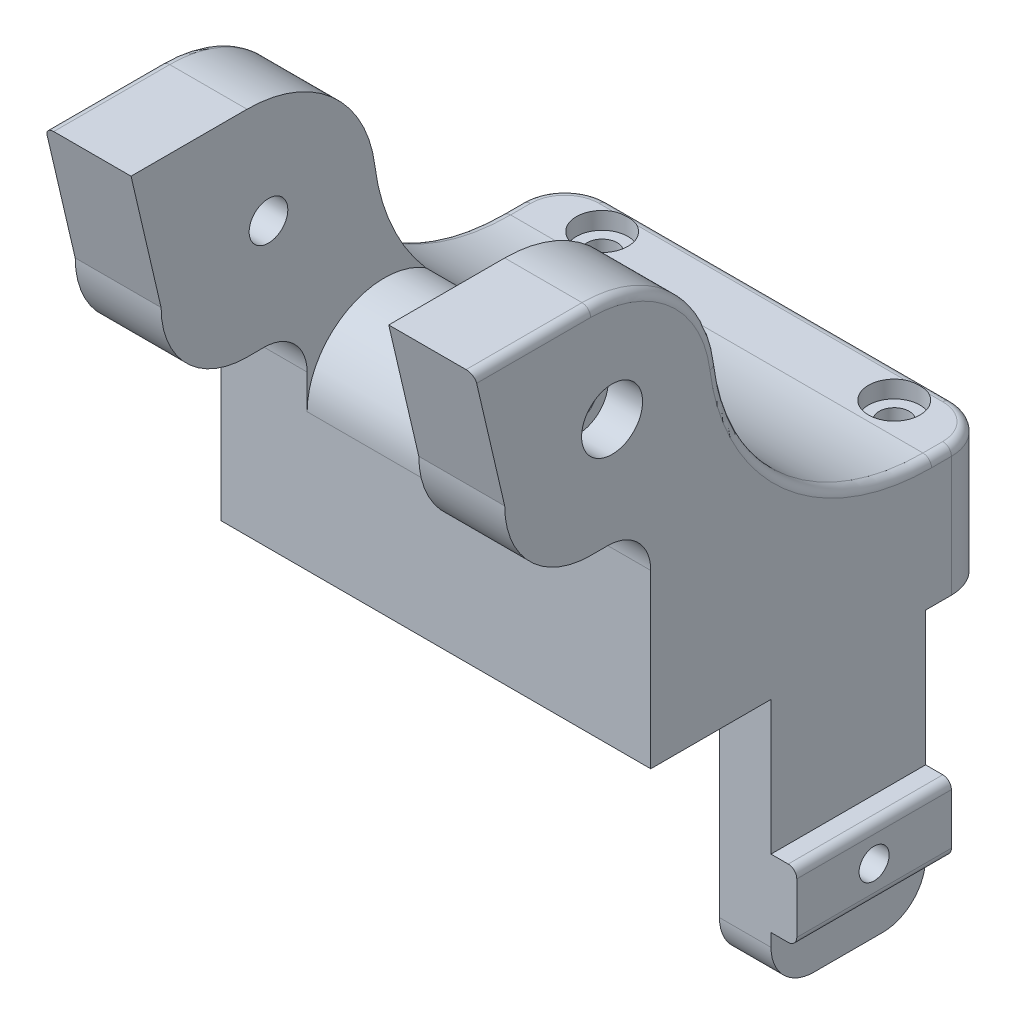
SolidWorks part; units mm, degrees
ref_plane "Alzado" through (0, 0, 0) normal (0, 0, 1) x (1, 0, 0)
ref_plane "Planta" through (0, 0, 0) normal (0, 1, 0) x (1, 0, 0)
ref_plane "Vista lateral" through (0, 0, 0) normal (1, 0, 0) x (0, 0, -1)
sketch "Croquis1" plane through (0, 0, 0) normal (0, 1, 0) x (1, 0, 0)
  line L1 (0, 0) -> (50, 0)
  line L2 (0, 0) -> (0, 40)
  line L3 (0, 40) -> (50, 40)
  line L4 (50, 0) -> (50, 40)
  dimension "D1" = 50
  dimension "D2" = 40
extrude "Saliente-Extruir1" add sketch "Croquis1" along normal blind 25
sketch "Croquis4" plane through (0, 25, 0) normal (0, 1, 0) x (1, 0, 0)
  line L0 (0, 40) -> (0, 0) construction
  line L1 (0, 8) -> (10, 8)
  line L2 (0, 8) -> (0, -17)
  line L3 (0, -17) -> (10, -17)
  line L4 (10, 8) -> (10, -17)
  line L5 (50, 0) -> (50, 40) construction
  line L6 (50, 8) -> (40, 8)
  line L7 (50, 8) -> (50, -17)
  line L8 (50, -17) -> (40, -17)
  line L9 (40, 8) -> (40, -17)
  line L10 (50, 40) -> (0, 40) construction
  dimension "D1" = 10
  dimension "D2" = 10
  dimension "D3" = 25
  dimension "D4" = 25
  dimension "D5" = 32
  dimension "D6" = 32
extrude "Saliente-Extruir3" add sketch "Croquis4" along normal blind 25
sketch "Croquis5" plane through (50, 0, 0) normal (1, 0, 0) x (0, 0, -1)
  line L0 (8, 50) -> (-17, 25) construction
  circle A0 centre (-4.5, 37.5) radius 2.25
  dimension "D1" = 4.5
extrude "Cortar-Extruir2" cut sketch "Croquis5" against normal up to surface (50 mm away) up to face at (0, 25, -7.75)
fillet "Redondeo4" radius 15 2 edges at (5, 50, -8) (45, 50, -8)
fillet "Redondeo5" radius 10 2 edges at (5, 25, 17) (45, 25, 17)
fillet "Redondeo6" radius 9 1 edges at (25, 25, 0)
sketch "Croquis6" plane through (0, 25, 0) normal (0, 1, 0) x (1, 0, 0)
  line L4 (0, 40) -> (0, 9)
  line L5 (0, 9) -> (50, 9)
  line L6 (50, 9) -> (50, 40)
  line L7 (50, 40) -> (0, 40)
  line L8 (0, 40) -> (0, 9)
  line L9 (0, 9) -> (50, 9)
  line L10 (50, 9) -> (50, 40)
  line L11 (50, 40) -> (0, 40)
  dimension "D1" = 0
extrude "Cortar-Extruir3" cut sketch "Croquis6" against normal blind 10
sketch "Croquis7" plane through (0, 0, -9) normal (0, 0, -1) x (-1, 0, 0)
  line L4 (0, 25) -> (-50, 25)
  line L5 (-50, 25) -> (-50, 15)
  line L6 (-50, 15) -> (0, 15)
  line L7 (0, 15) -> (0, 25)
  line L8 (0, 25) -> (-50, 25)
  line L9 (-50, 25) -> (-50, 15)
  line L10 (-50, 15) -> (0, 15)
  line L11 (0, 15) -> (0, 25)
  dimension "D1" = 0
extrude "Cortar-Extruir4" cut sketch "Croquis7" against normal up to surface (1 mm away) up to face at (5, 29.9721, -8)
fillet "Redondeo7" radius 25 1 edges at (25, 15, -8)
fillet "Redondeo8" radius 5 2 edges at (45, 25, 0) (5, 25, 0)
sketch "Croquis8" plane through (0, 15, 0) normal (0, 1, 0) x (1, 0, 0)
  line L0 (0, 36.3431) -> (50, 36.3431) construction
  line L1 (0, 40) -> (0, 32.6863) construction
  line L2 (50, 32.6863) -> (50, 40) construction
  circle A0 centre (8, 36.3431) radius 1.75
  circle A1 centre (42, 36.3431) radius 1.75
  dimension "D1" = 3.5
  dimension "D2" = 3.5
  dimension "D3" = 8
  dimension "D4" = 8
extrude "Cortar-Extruir5" cut sketch "Croquis8" against normal up to surface (15 mm away) up to face at (25, 0, -20)
sketch "Croquis9" plane through (0, 15, 0) normal (0, 1, 0) x (1, 0, 0)
  circle A0 centre (8, 36.3431) radius 3
  circle A1 centre (42, 36.3431) radius 3
  dimension "D1" = 6
  dimension "D2" = 6
extrude "Cortar-Extruir6" cut sketch "Croquis9" against normal blind 2
fillet "Redondeo9" radius 5 2 edges at (0, 7.5, -40) (50, 7.5, -40)
sketch "Croquis10" plane through (0, 0, 0) normal (0, -1, 0) x (1, 0, 0)
  line L0 (0, -35) -> (0, 0) construction
  line L1 (0, -32) -> (6, -32)
  line L2 (0, -32) -> (0, -14)
  line L3 (0, -14) -> (6, -14)
  line L4 (6, -32) -> (6, -14)
  line L5 (45, -40) -> (5, -40) construction
  dimension "D1" = 18
  dimension "D2" = 8
  dimension "D3" = 6
extrude "Saliente-Extruir4" add sketch "Croquis10" along normal blind 30
sketch "Croquis11" plane through (0, 0, 0) normal (-1, 0, 0) x (0, 0, 1)
  line L0 (-32, -30) -> (-32, 0) construction
  line L1 (-32, -23.5) -> (-14, -23.5)
  line L2 (-32, -23.5) -> (-32, -15.6)
  line L3 (-32, -15.6) -> (-14, -15.6)
  line L4 (-14, -23.5) -> (-14, -15.6)
  line L5 (-14, -30) -> (-14, 0) construction
  line L6 (-14, -30) -> (-32, -30) construction
  dimension "D1" = 6.5
  dimension "D2" = 7.9
extrude "Saliente-Extruir5" add sketch "Croquis11" along normal blind 3
fillet "Redondeo10" radius 1 2 edges at (-3, -23.5, -23) (-3, -15.6, -23)
sketch "Croquis12" plane through (-3, 0, 0) normal (-1, 0, 0) x (0, 0, 1)
  line L0 (-32, -19.55) -> (-14, -19.55) construction
  line L1 (-32, -16.6) -> (-32, -22.5) construction
  line L2 (-14, -22.5) -> (-14, -16.6) construction
  circle A0 centre (-28, -19.55) radius 1.75
  circle A1 centre (-18, -19.55) radius 1.75
  dimension "D1" = 3.5
  dimension "D2" = 3.5
  dimension "D3" = 4
  dimension "D4" = 4
extrude "Cortar-Extruir7" cut sketch "Croquis12" against normal up to surface (9 mm away) up to face at (6, -15, -23)
sketch "Croquis13" plane through (6, 0, 0) normal (1, 0, 0) x (0, 0, -1)
  circle A0 centre (28, -19.55) radius 3
  circle A1 centre (18, -19.55) radius 3
  dimension "D1" = 6
  dimension "D2" = 6
extrude "Cortar-Extruir8" cut sketch "Croquis13" against normal blind 1.5
sketch "Croquis16" plane through (0, 0, 0) normal (0, -1, 0) x (1, 0, 0)
  line L0 (25, -40) -> (25, 0) construction
  line L1 (45, -40) -> (5, -40) construction
  line L2 (0, 0) -> (50, 0) construction
  circle A0 centre (25, -25.3431) radius 1.75
  circle A1 centre (8, -36.3431) radius 1.75 construction
  dimension "D1" = 3.5
  dimension "D2" = 11
extrude "Cortar-Extruir9" cut sketch "Croquis16" against normal through all
ref_plane "Plano1" through (0, 20, 0) normal (0, 1, 0) x (1, 0, 0)
sketch "Croquis17" plane through (0, 20, 0) normal (0, 1, 0) x (1, 0, 0)
  circle A0 centre (25, 25.3431) radius 3
  dimension "D1" = 6
extrude "Cortar-Extruir10" cut sketch "Croquis17" against normal blind 8
fillet "Redondeo11" radius 5 2 edges at (3, -30, -14) (3, -30, -32)
sketch "Croquis18" plane through (0, 0, 0) normal (0, -1, 0) x (1, 0, 0)
  line L0 (50, 0) -> (50, -35) construction
  line L1 (50, -32) -> (44, -32)
  line L2 (50, -32) -> (50, -14)
  line L3 (50, -14) -> (44, -14)
  line L4 (44, -32) -> (44, -14)
  line L5 (45, -40) -> (5, -40) construction
  dimension "D1" = 18
  dimension "D2" = 6
  dimension "D3" = 8
extrude "Saliente-Extruir6" add sketch "Croquis18" along normal blind 30
sketch "Croquis19" plane through (50, 0, 0) normal (1, 0, 0) x (0, 0, -1)
  line L0 (32, -30) -> (32, 0) construction
  line L1 (32, -15.6) -> (14, -15.6)
  line L2 (32, -15.6) -> (32, -23.5)
  line L3 (32, -23.5) -> (14, -23.5)
  line L4 (14, -15.6) -> (14, -23.5)
  line L5 (14, -30) -> (14, 0) construction
  line L6 (32, -30) -> (14, -30) construction
  point P8 (23, -23.5)
  dimension "D1" = 7.9
  dimension "D2" = 6.5
extrude "Saliente-Extruir7" add sketch "Croquis19" along normal blind 3
sketch "Croquis20" plane through (53, 0, 0) normal (1, 0, 0) x (0, 0, -1)
  line L0 (32, -19.55) -> (14, -19.55) construction
  line L1 (32, -23.5) -> (32, -15.6) construction
  line L2 (14, -15.6) -> (14, -23.5) construction
  line L3 (23, -23.5) -> (23, -15.6) construction
  line L4 (14, -23.5) -> (32, -23.5) construction
  line L5 (32, -15.6) -> (14, -15.6) construction
  circle A0 centre (23, -19.55) radius 1.75
  dimension "D1" = 3.5
extrude "Cortar-Extruir11" cut sketch "Croquis20" against normal up to surface (9 mm away) up to face at (44, -15, -23)
sketch "Croquis21" plane through (44, 0, 0) normal (-1, 0, 0) x (0, 0, 1)
  circle A0 centre (-23, -19.55) radius 3
  dimension "D1" = 6
extrude "Cortar-Extruir12" cut sketch "Croquis21" against normal blind 1.5
fillet "Redondeo13" radius 1 2 edges at (53, -15.6, -23) (53, -23.5, -23)
fillet "Redondeo14" radius 5 2 edges at (47, -30, -14) (47, -30, -32)
sketch "Croquis22" plane through (0, 0, -32) normal (0, 0, -1) x (-1, 0, 0)
  line L1 (-6, 0) -> (3.2219, 0)
  line L2 (-6, 0) -> (-6, -30.8775)
  line L3 (-6, -30.8775) -> (3.2219, -30.8775)
  line L4 (3.2219, 0) -> (3.2219, -30.8775)
extrude "Cortar-Extruir13" cut sketch "Croquis22" against normal through all
sketch "Croquis23" plane through (50, 0, 0) normal (1, 0, 0) x (0, 0, -1)
  circle A0 centre (-4.5, 37.5) radius 3.55
  dimension "D1" = 7.1
extrude "Cortar-Extruir14" cut sketch "Croquis23" against normal blind 4
sketch "Croquis24" plane through (0, 0, 0) normal (-1, 0, 0) x (0, 0, 1)
  line L0 (-35, 0) -> (0, 0) construction
  line L1 (2.3927, 33.85) -> (6.6073, 33.85)
  line L2 (6.6073, 33.85) -> (8.7147, 37.5)
  line L3 (8.7147, 37.5) -> (6.6073, 41.15)
  line L4 (6.6073, 41.15) -> (2.3927, 41.15)
  line L5 (2.3927, 41.15) -> (0.2853, 37.5)
  line L6 (0.2853, 37.5) -> (2.3927, 33.85)
  circle A0 centre (4.5, 37.5) radius 3.65 construction
  dimension "D1" = 7.3
extrude "Cortar-Extruir15" cut sketch "Croquis24" against normal blind 4
sketch "Croquis25" plane through (0, 0, 0) normal (-1, 0, 0) x (0, 0, 1)
  line L0 (17, 50) -> (20.5, 50)
  line L1 (20.5, 50) -> (17, 35)
  line L2 (17, 35) -> (17, 50)
  point P6 (17, 34.785)
  dimension "D1" = 3.5
extrude "Saliente-Extruir8" add sketch "Croquis25" against normal up to surface (10 mm away) up to face at (10, 37.5, 6.75)
sketch "Croquis26" plane through (50, 0, 0) normal (1, 0, 0) x (0, 0, -1)
  line L0 (-17, 50) -> (-20.5, 50)
  line L1 (-20.5, 50) -> (-17, 35)
  line L2 (-17, 35) -> (-17, 50)
extrude "Saliente-Extruir9" add sketch "Croquis26" against normal up to surface (10 mm away) up to face at (40, 37.5, 2.25)
fillet "Redondeo15" radius 1 11 edges at (0, 50, 13.75) (0, 46.25, -2.9216) (0, 21.25, -16.1503) (0, 15, -33.8431) (1.4645, 15, -38.5355) (25, 15, -40) (48.5355, 15, -38.5355) (50, 15, -33.8431) (50, 50, 13.75) (50, 46.25, -2.9216) (50, 21.25, -16.1503)
